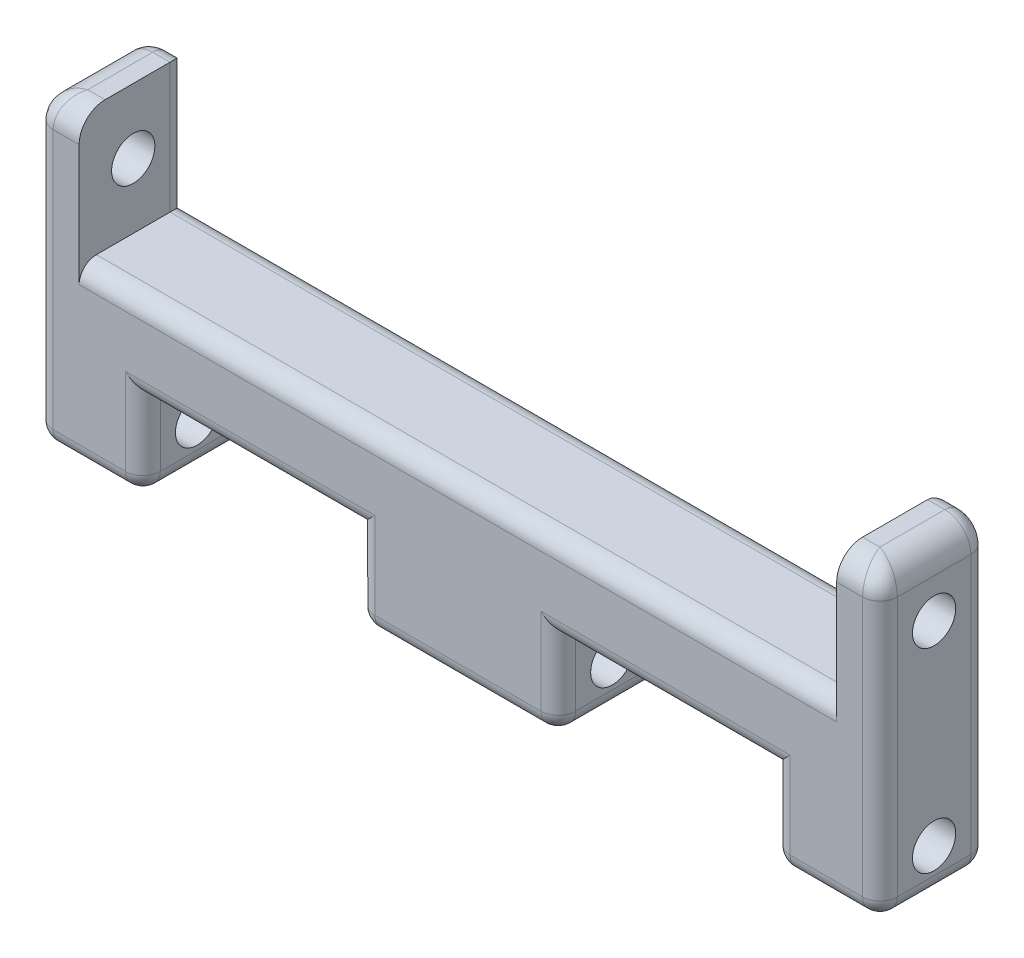
SolidWorks part; units mm, degrees
ref_plane "Front" through (0, 0, 0) normal (0, 0, 1) x (1, 0, 0)
ref_plane "Top" through (0, 0, 0) normal (0, 1, 0) x (1, 0, 0)
ref_plane "Right" through (0, 0, 0) normal (1, 0, 0) x (0, 0, -1)
sketch "Эскиз1" plane through (0, 0, 0) normal (0, 0, 1) x (1, 0, 0)
  line L0 (0, 0) -> (0, -3)
  line L1 (0, -3) -> (17.5, -3)
  line L2 (17.5, -3) -> (17.5, 0)
  line L3 (0, 0) -> (-1, 0)
  line L4 (-1, 0) -> (-1, -7)
  line L5 (8.75, -3) -> (8.75, -28.8234) construction
  line L6 (-1, -7) -> (1.475, -7)
  line L7 (1.475, -7) -> (1.475, -5)
  line L8 (1.475, -5) -> (6.4328, -5)
  line L9 (6.4328, -5) -> (6.4328, -7)
  line L10 (6.4328, -7) -> (11.0672, -7)
  line L11 (17.5, 0) -> (18.5, 0)
  line L12 (18.5, 0) -> (18.5, -7)
  line L13 (18.5, -7) -> (16.025, -7)
  line L14 (16.025, -7) -> (16.025, -5)
  line L15 (16.025, -5) -> (11.0672, -5)
  line L16 (11.0672, -5) -> (11.0672, -7)
  point P20 (8.75, -7)
  dimension "D1" = 17.5
  dimension "D2" = 3
  dimension "D3" = 7
  dimension "D4" = 2
  dimension "D5" = 1
extrude "Бобышка-Вытянуть1" add sketch "Эскиз1" along normal blind 2.5
sketch "Эскиз2" plane through (18.5, 0, 0) normal (1, 0, 0) x (0, 0, -1)
  line L0 (-2.5, 0) -> (0, 0) construction
  line L1 (-2.5, -7) -> (0, -7) construction
  circle A0 centre (-1.25, -1.5) radius 0.5
  circle A1 centre (-1.25, -6) radius 0.5
  point P2 (-1.25, 0)
  dimension "D1" = 1
  dimension "D2" = 1.5
  dimension "D3" = 1
extrude "Вырез-Вытянуть1" cut sketch "Эскиз2" against normal through all
fillet "Скругление1" radius 0.4 33 edges at (-0.5, 0, 0) (18, 0, 0) (17.5, -1.5, 0) (0, -1.5, 0) (8.75, -3, 0) (6.4328, -6, 0) (-1, -3.5, 0) (0.2375, -7, 0) (18.5, -3.5, 0) (18.5, -3.5, 2.5) (-1, -3.5, 2.5) (11.0672, -6, 0) (1.475, -6, 0) (3.9539, -5, 0) (17.2625, -7, 0) (13.5461, -5, 0) (8.75, -7, 0) (8.75, -3, 2.5) (8.75, -7, 2.5) (6.4328, -6, 2.5) (11.0672, -6, 2.5) (13.5461, -5, 2.5) (16.025, -6, 2.5) (17.2625, -7, 2.5) (16.025, -7, 1.25) (1.475, -7, 1.25) (1.475, -6, 2.5) (3.9539, -5, 2.5) (6.4328, -7, 1.25) (11.0672, -7, 1.25) (18.5, -7, 1.25) (-1, -7, 1.25) (0.2375, -7, 2.5)
fillet "Скругление2" radius 0.6 8 edges at (-0.8828, -0.1172, 0.1172) (18.3828, -0.1172, 0.1172) (17.8, 0, 2.5) (18.3828, 0, 2.3828) (-0.3, 0, 2.5) (-0.8828, 0, 2.3828) (18.5, 0, 1.25) (-1, 0, 1.25)
